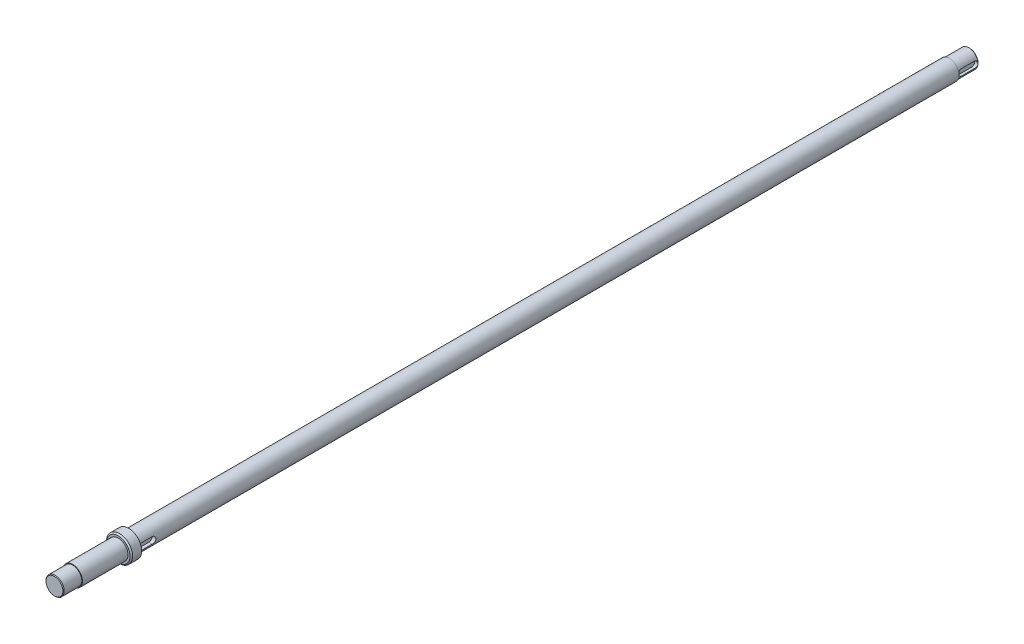
SolidWorks part; units mm, degrees
ref_plane "前视基准面" through (0, 0, 0) normal (0, 0, 1) x (1, 0, 0)
ref_plane "上视基准面" through (0, 0, 0) normal (0, 1, 0) x (1, 0, 0)
ref_plane "右视基准面" through (0, 0, 0) normal (1, 0, 0) x (0, 0, -1)
other "Configuration Table"
sketch "草图1" plane through (0, 0, 0) normal (1, 0, 0) x (0, 0, -1)
  line L0 (0, 0) -> (0, 7)
  line L1 (0, 7) -> (14, 7)
  line L2 (14, 7) -> (14, 7.5)
  line L3 (14, 7.5) -> (49, 7.5)
  line L4 (49, 7.5) -> (49, 10)
  line L5 (49, 10) -> (57, 10)
  line L6 (57, 10) -> (57, 7.5)
  line L7 (57, 7.5) -> (687.5, 7.5)
  line L8 (687.5, 7.5) -> (687.5, 7)
  line L9 (687.5, 7) -> (703, 7)
  line L10 (703, 7) -> (703, 0)
  line L11 (703, 0) -> (0, 0)
  line L12 (0, 0) -> (-37.1247, 0) construction
  dimension "D1" = 14
  dimension "D2" = 15
  dimension "D3" = 20
  dimension "D4" = 14
  dimension "D5" = 35
  dimension "D6" = 8
  dimension "D7" = 673.5
  dimension "D8" = 15.5
revolve "旋转1" add sketch "草图1" angle 360 about L12
ref_plane "基准面1" through (4.5, 0, 0) normal (1, 0, 0) x (0, 0, -1)
sketch "草图2" plane through (4.5, 0, 0) normal (1, 0, 0) x (0, 0, -1)
  line L0 (60, 0) -> (68, 0) construction
  line L1 (60, 2.5) -> (68, 2.5)
  line L2 (60, -2.5) -> (68, -2.5)
  line L3 (690, 0) -> (700, 0) construction
  line L4 (690, 2.5) -> (700, 2.5)
  line L5 (690, -2.5) -> (700, -2.5)
  line L6 (57, -7.5) -> (57, 7.5) construction
  line L7 (687.5, -7.5) -> (687.5, 7.5) construction
  arc A0 (60, 2.5) -> (60, -2.5) centre (60, 0) ccw
  arc A1 (68, -2.5) -> (68, 2.5) centre (68, 0) ccw
  arc A2 (690, 2.5) -> (690, -2.5) centre (690, 0) ccw
  arc A3 (700, -2.5) -> (700, 2.5) centre (700, 0) ccw
  point P2 (64, 0)
  point P10 (695, 0)
  dimension "D1" = 8
  dimension "D2" = 3
  dimension "D3" = 5
  dimension "D4" = 10
  dimension "D5" = 5
extrude "切除-拉伸1" cut sketch "草图2" along normal through all contours L2 A1 L1 A0 | L5 A3 L4 A2
chamfer "倒角1" distance 1 angle 45 1 edges at (-10, 0, -49)
sketch "草图3" plane through (0, 0, -703) normal (0, 0, -1) x (-1, 0, 0)
  circle A0 centre (0, 0) radius 3
  dimension "D1" = 6
extrude "切除-拉伸2" cut sketch "草图3" against normal blind 15
chamfer "倒角2" distance 0.5 angle 45 3 edges at (-7, 0, -703) (-7, 0, 0) (-3, 0, -703)
